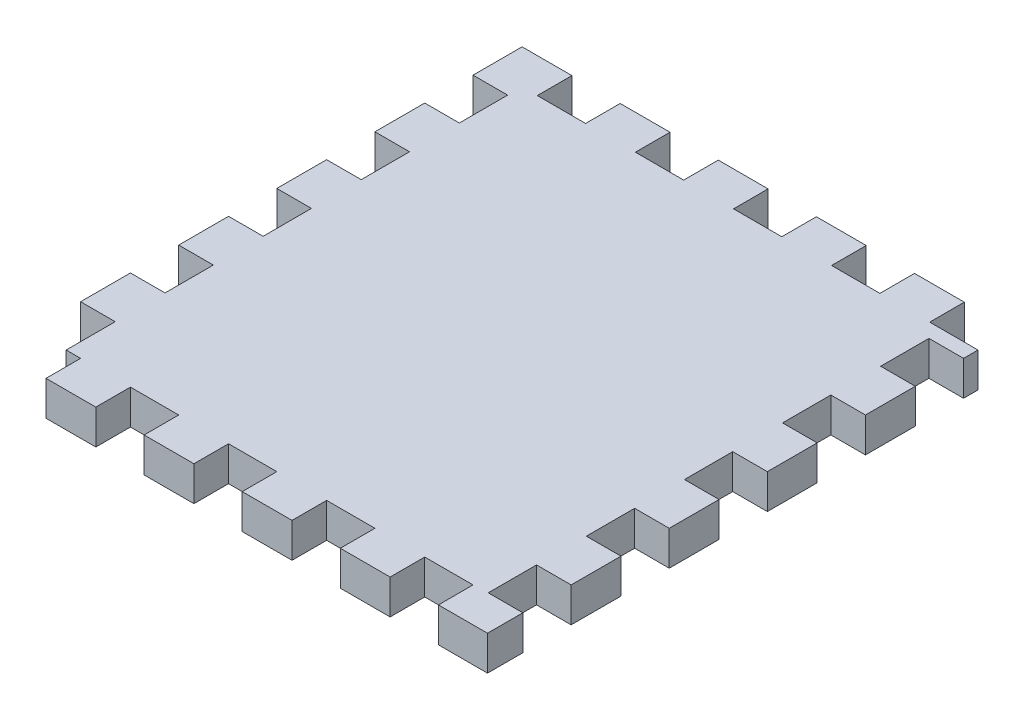
SolidWorks part; units mm, degrees
material "Acrylic (Medium-high impact)"
ref_plane "Front Plane" through (0, 0, 0) normal (0, 0, 1) x (1, 0, 0)
ref_plane "Top Plane" through (0, 0, 0) normal (0, 1, 0) x (1, 0, 0)
ref_plane "Right Plane" through (0, 0, 0) normal (1, 0, 0) x (0, 0, -1)
sketch "Sketch2" plane through (0, 0, 0) normal (0, 1, 0) x (1, 0, 0)
  line L1 (-22.5, 22.5) -> (22.5, 22.5)
  line L2 (-22.5, 22.5) -> (-22.5, -22.5)
  line L3 (-22.5, -22.5) -> (22.5, -22.5)
  line L4 (22.5, 22.5) -> (22.5, -22.5)
  line L5 (-22.5, 22.5) -> (22.5, -22.5) construction
  line L6 (-22.5, -22.5) -> (22.5, 22.5) construction
  point P0 (0, 0)
  dimension "D1" = 45
  dimension "D2" = 45
extrude "Boss-Extrude1" add sketch "Sketch2" along normal mid plane 3.175
sketch "Sketch4" plane through (0, 0, -22.5) normal (0, 0, -1) x (-1, 0, 0)
  line L0 (-22.5, -1.5875) -> (22.5, -1.5875) construction
  line L1 (22.5, 1.5875) -> (17.93, 1.5875)
  line L2 (22.5, 1.5875) -> (22.5, -1.5875)
  line L3 (22.5, -1.5875) -> (17.93, -1.5875)
  line L4 (17.93, 1.5875) -> (17.93, -1.5875)
  dimension "D1" = 4.57
extrude "Boss-Extrude2" add sketch "Sketch4" along normal blind 3.175
sketch "Sketch5" plane through (0, 0, 22.5) normal (0, 0, 1) x (1, 0, 0)
  line L0 (-22.5, 1.5875) -> (22.5, 1.5875) construction
  line L1 (-22.43, -1.5875) -> (-18, -1.5875)
  line L2 (-22.43, -1.5875) -> (-22.43, 1.5875)
  line L3 (-22.43, 1.5875) -> (-18, 1.5875)
  line L4 (-18, -1.5875) -> (-18, 1.5875)
  line L5 (-22.5, 1.5875) -> (-22.5, -1.5875) construction
  line L6 (-22.5, -1.5875) -> (22.5, -1.5875) construction
  dimension "D1" = 4.43
  dimension "D2" = 0.07
extrude "Cut-Extrude2" cut sketch "Sketch5" against normal blind 3.175
pattern_linear "LPattern1" count 5 spacing 9 along (1, 0, 0) of "Cut-Extrude2"
pattern_linear "LPattern2" count 5 spacing 9 along (1, 0, 0) of "Boss-Extrude2"
sketch "Sketch7" plane through (-22.5, 0, 0) normal (-1, 0, 0) x (0, 0, 1)
  line L0 (-25.675, 1.5875) -> (22.5, 1.5875) construction
  line L1 (-22.5, 1.5875) -> (-18.07, 1.5875)
  line L2 (-22.5, 1.5875) -> (-22.5, -1.5875)
  line L3 (-22.5, -1.5875) -> (-18.07, -1.5875)
  line L4 (-18.07, 1.5875) -> (-18.07, -1.5875)
  line L5 (-25.675, -1.5875) -> (22.5, -1.5875) construction
  line L6 (-25.675, -1.5875) -> (-25.675, 1.5875) construction
  dimension "D1" = 3.175
  dimension "D2" = 4.43
extrude "Cut-Extrude3" [suppressed] cut sketch "Sketch7" against normal blind 3.175
sketch "Sketch8" [suppressed] plane through (-20.9125, 0, 0) normal (-1, 0, 0) x (0, 0, 1)
  line L0 (-20.9125, 1.5875) -> (20.9125, 1.5875) construction
  line L1 (-20.9125, -1.5875) -> (-16.3425, -1.5875)
  line L2 (-20.9125, -1.5875) -> (-20.9125, 1.5875)
  line L3 (-20.9125, 1.5875) -> (-16.3425, 1.5875)
  line L4 (-16.3425, -1.5875) -> (-16.3425, 1.5875)
  dimension "D1" = 4.57
extrude "Boss-Extrude3" [suppressed] add sketch "Sketch8" along normal blind 3.175
pattern_linear "LPattern3" [suppressed] count 5 spacing 9 of bodies 108
ref_axis "Axis1" through (0, 0, 0) along (0, 1, 0)
pattern_circular "CirPattern1" [suppressed] count 4 every 90 about axis through (0, 0, 0) along (0, 1, 0) of bodies 109
sketch "Sketch9" plane through (-22.5, 0, 0) normal (-1, 0, 0) x (0, 0, 1)
  line L0 (-25.675, -1.5875) -> (22.5, -1.5875) construction
  line L1 (19.255, 1.5875) -> (14.825, 1.5875)
  line L2 (19.255, 1.5875) -> (19.255, -1.5875)
  line L3 (19.255, -1.5875) -> (14.825, -1.5875)
  line L4 (14.825, 1.5875) -> (14.825, -1.5875)
  line L7 (-25.675, 1.5875) -> (22.5, 1.5875) construction
  line L8 (22.5, 1.5875) -> (22.5, -1.5875) construction
  dimension "D1" = 4.43
  dimension "D2" = 3.245
sketch "Sketch10" plane through (0, 0, 22.5) normal (0, 0, 1) x (1, 0, 0)
  line L1 (-22.5, 1.5875) -> (-22.43, 1.5875)
  line L2 (-22.5, 1.5875) -> (-22.5, -1.5875)
  line L3 (-22.5, -1.5875) -> (-22.43, -1.5875)
  line L4 (-22.43, 1.5875) -> (-22.43, -1.5875)
extrude "Cut-Extrude5" cut sketch "Sketch10" against normal blind 3.175
extrude "Cut-Extrude4" cut sketch "Sketch9" against normal blind 3.175
sketch "Sketch11" plane through (-22.5, 0, 0) normal (-1, 0, 0) x (0, 0, 1)
  line L1 (19.255, 1.5875) -> (19.325, 1.5875)
  line L2 (19.255, 1.5875) -> (19.255, -1.5875)
  line L3 (19.255, -1.5875) -> (19.325, -1.5875)
  line L4 (19.325, 1.5875) -> (19.325, -1.5875)
extrude "Cut-Extrude6" cut sketch "Sketch11" against normal blind 3.175
pattern_linear "LPattern4" count 5 spacing 9 along (0, 0, -1) of "Cut-Extrude4"
sketch "Sketch14" plane through (22.5, 0, 0) normal (1, 0, 0) x (0, 0, -1)
  line L0 (-22.5, 1.5875) -> (22.5, 1.5875) construction
  line L1 (-19.255, 1.5875) -> (-14.825, 1.5875)
  line L2 (-19.255, 1.5875) -> (-19.255, -1.5875)
  line L3 (-19.255, -1.5875) -> (-14.825, -1.5875)
  line L4 (-14.825, 1.5875) -> (-14.825, -1.5875)
  line L5 (-22.5, -1.5875) -> (22.5, -1.5875) construction
  line L7 (-22.5, 1.5875) -> (-22.5, -1.5875) construction
  dimension "D2" = 4.43
  dimension "D1" = 3.245
extrude "Cut-Extrude7" cut sketch "Sketch14" against normal blind 3.175
pattern_linear "LPattern5" count 5 spacing 9 along (0, 0, -1) of "Cut-Extrude7"
sketch "Sketch15" [suppressed] plane through (0, 1.5875, 0) normal (0, 1, 0) x (1, 0, 0)
  circle A0 centre (0, 0) radius 17.5
  dimension "D1" = 35
extrude "Cut-Extrude8" [suppressed] cut sketch "Sketch15" against normal through all
equation "\"D1@Sketch2\"  = 65-3.175"
equation "\"width\"= 3.175mm"
equation "\"D2@Sketch2\" = 65-\"width\""
equation "\"kerf\"= 0.07mm"
equation "\"D1@Sketch4\"   = 4.5 + \"kerf\""
equation "\"D2@Sketch7\"   = 4.5 - \"kerf\""
equation "\"D1@Sketch8\"= 4.5 + \"kerf\""
equation "\"D1@Sketch9\"   = 4.5 - \"kerf\""
equation "\"D2@Sketch9\"=\"width\"+\"kerf\""
equation "\"D2@Sketch14\"  = 4.5 - \"kerf\""
equation "\"D1@Sketch14\"=\"width\"+\"kerf\""
equation "\"D1@Sketch5\"=4.5-\"kerf\""
equation "\"D2@Sketch3\"=6.5+\"kerf\""
